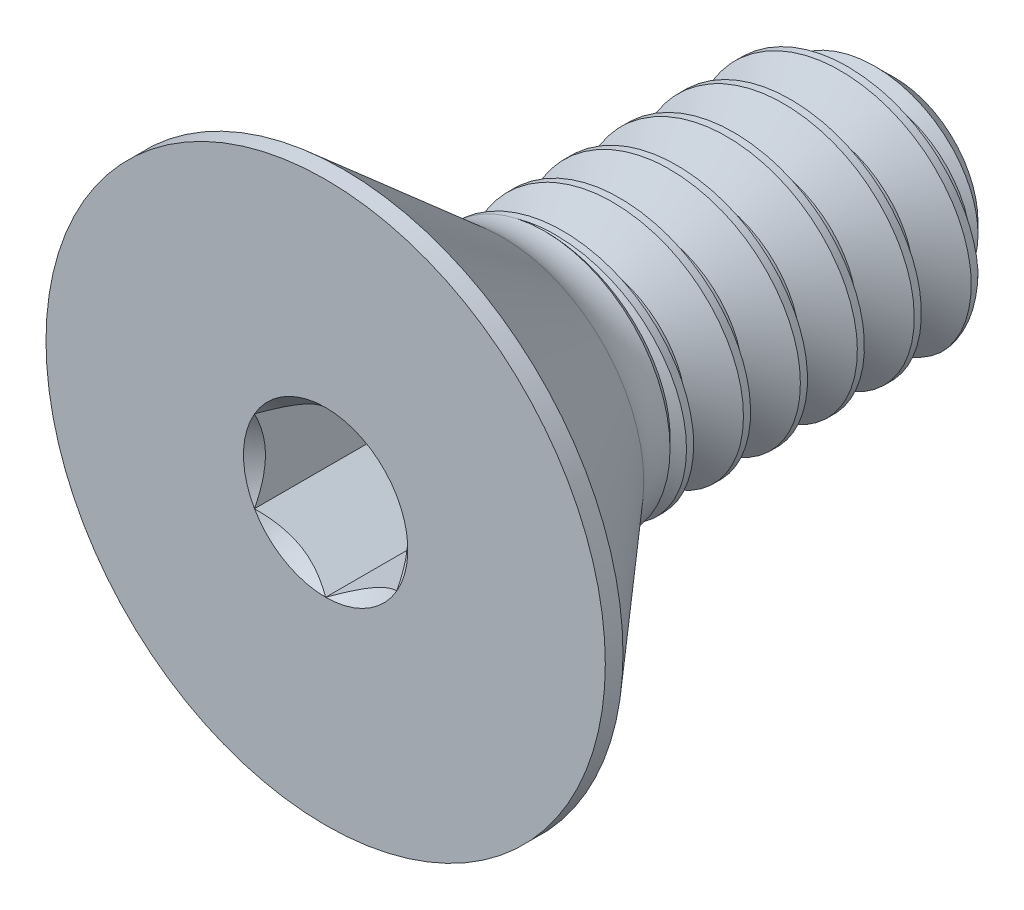
SolidWorks part; units mm, degrees
ref_plane "Front" through (0, 0, 0) normal (0, 0, 1) x (1, 0, 0)
ref_plane "Top" through (0, 0, 0) normal (0, 1, 0) x (1, 0, 0)
ref_plane "Right" through (0, 0, 0) normal (1, 0, 0) x (0, 0, -1)
sketch "Sketch1" plane through (0, 0, 0) normal (1, 0, 0) x (0, 0, -1)
  line L0 (0, 3.8989) -> (0.2464, 3.8989) construction
  line L1 (0.2464, 3.8989) -> (2.4638, 1.9713) construction
  line L2 (0, 1.7526) -> (7.9375, 1.7526)
  line L3 (7.9375, 1.7526) -> (7.9375, 0)
  line L4 (7.9375, 0) -> (0, 0)
  line L5 (0, 0) -> (0, 3.8989) construction
  line L6 (0, 3.8989) -> (0, -3.8989) construction
  line L7 (7.9375, 1.7526) -> (7.9375, -1.7526) construction
  line L8 (0, -3.8989) -> (0.2464, -3.8989) construction
  line L9 (0.2464, -3.8989) -> (2.4638, -1.9713) construction
  line L11 (0, 1.7526) -> (0, 0)
  line L12 (3.0488, 1.7526) -> (3.0488, 0) construction
  arc A1 (2.4638, 1.9713) -> (3.0488, 1.7526) centre (3.0488, 2.6443) ccw construction
  dimension "D1" = 0.2464
revolve "Revolve1" add sketch "Sketch1" angle 360 mid plane about L4
sketch "Sketch3" plane through (0, 0, -7.9375) normal (0, 0, -1) x (-1, 0, 0)
  circle A0 centre (0, 0) radius 1.7526
curve "Helix/Spiral1" pitch 0.7937 height 7.9375 radius 1.7526 centre (0, 0, -7.9375) axis (0, 0, 1) start towards (0, 1, 0)
sketch "Sketch2" plane through (0, 0, 0) normal (1, 0, 0) x (0, 0, -1)
  line L0 (7.9375, 1.7526) -> (8.632, 1.7526)
  line L1 (8.632, 1.7526) -> (8.3344, 1.237)
  line L2 (8.3344, 1.237) -> (8.2352, 1.237)
  line L3 (8.2352, 1.237) -> (7.9375, 1.7526)
  line L4 (8.0863, 1.4948) -> (8.4832, 1.4948) construction
  dimension "D1" = 60
  dimension "D2" = 0.0992
  dimension "D3" = 0.3969
chamfer "Chamfer1" distance 0.5953 angle 45 1 edges at (0, 1.7526, -7.9375)
sweep "Cut-Sweep1" cut profiles "Sketch2" path "Helix/Spiral1" align with end faces yes
sketch "Sketch7" plane through (0, 0, 0) normal (1, 0, 0) x (0, 0, -1)
  line L0 (0, 3.8989) -> (0.2464, 3.8989) construction
  line L1 (0.2464, 3.8989) -> (2.4638, 1.9713) construction
  line L2 (0, 3.8989) -> (0.2464, 3.8989)
  line L3 (0.2464, 3.8989) -> (2.4638, 1.9713)
  line L4 (3.0488, 1.7526) -> (3.0488, 0) construction
  line L5 (3.0488, 1.7526) -> (3.0488, 0)
  line L7 (0, 0) -> (0, 3.8989) construction
  line L8 (0, 0) -> (0, 3.8989)
  line L9 (0, 0) -> (3.0488, 0)
  line L10 (4.2888, 0) -> (-4.2888, 0) construction
  arc A0 (2.4638, 1.9713) -> (3.0488, 1.7526) centre (3.0488, 2.6443) ccw construction
  arc A1 (2.4638, 1.9713) -> (3.0488, 1.7526) centre (3.0488, 2.6443) ccw
revolve "Revolve2" add sketch "Sketch7" angle 360 mid plane about L9
ref_plane "Plane1" through (0, 0, -3.0488) normal (0, 0, 1) x (1, 0, 0)
sketch "Sketch8" plane through (0, 0, -3.0488) normal (0, 0, 1) x (1, 0, 0)
  circle A0 centre (0, 0) radius 1.7526
extrude "Boss-Extrude1" add sketch "Sketch8" against normal through all draft 45
sketch "Sketch5" plane through (0, 0, 0) normal (0, 0, 1) x (1, 0, 0)
  line L1 (0.9922, -0.5728) -> (0.9922, 0.5728)
  line L2 (0.9922, 0.5728) -> (0, 1.1457)
  line L3 (0, 1.1457) -> (-0.9922, 0.5728)
  line L4 (-0.9922, 0.5728) -> (-0.9922, -0.5728)
  line L5 (-0.9922, -0.5728) -> (0, -1.1457)
  line L6 (0, -1.1457) -> (0.9922, -0.5728)
  circle A0 centre (0, 0) radius 0.9922 construction
  dimension "Hex" = 1.9844
extrude "Cut-Extrude2" cut sketch "Sketch5" against normal blind 1.7247
sketch "Sketch6" plane through (0, 0, 0) normal (0, 0, 1) x (1, 0, 0)
  circle A0 centre (0, 0) radius 1.1457
extrude "Cut-Extrude3" cut sketch "Sketch6" against normal blind 1.7247 draft 45
sketch "Sketch9" [suppressed] plane through (0, 0, -3.0488) normal (0, 0, 1) x (1, 0, 0)
  circle A1 centre (0, 0) radius 1.7526
  circle A2 centre (0, 0) radius 1.7526
  point P0 (0, 1.7526)
  dimension "D1" = 0
extrude "Boss-Extrude2" [suppressed] add sketch "Sketch9" against normal offset from surface (28.7012 mm away) 22.225 up to face at (0, 1.1573, -7.9375)
sketch "Sketch10" plane through (0, 0, 0) normal (1, 0, 0) x (0, 0, -1)
  line L0 (7.9375, 1.7526) -> (7.9375, -1.7526) construction
  point P0 (6.7469, -1.7526)
  dimension "D1" = 1.1906
equation "\"D3@Helix/Spiral1\" = \"Lg@Sketch1\""
equation "\"D2@Sketch2\" = \"D4@Helix/Spiral1\" * .125"
equation "\"D3@Sketch2\" = \"D4@Helix/Spiral1\" * .5"
equation "\"D1@Chamfer1\" = \"D4@Helix/Spiral1\" * .75"
equation "\"D1@Cut-Extrude2\" = \"Head Ht@Sketch1\" * .7"
equation "\"D1@Sketch1\" = \"Head Ht@Sketch1\" * .1"
equation "\"D1@Sketch10\" = \"D4@Helix/Spiral1\" * 1.5"
equation "\"D1@Cut-Extrude3\" = \"D1@Cut-Extrude2\""
